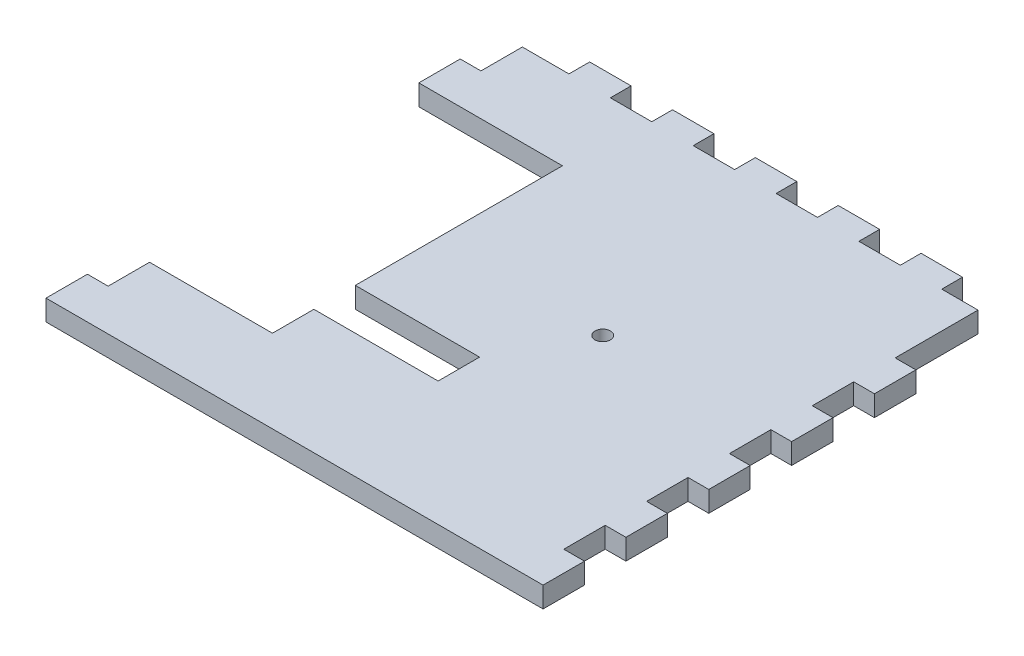
SolidWorks part; units mm, degrees
ref_plane "Front Plane" through (0, 0, 0) normal (0, 0, 1) x (1, 0, 0)
ref_plane "Top Plane" through (0, 0, 0) normal (0, 1, 0) x (1, 0, 0)
ref_plane "Right Plane" through (0, 0, 0) normal (1, 0, 0) x (0, 0, -1)
sketch "Sketch1" plane through (0, 0, 0) normal (0, 1, 0) x (1, 0, 0)
  line L1 (-139.7, -139.7) -> (139.7, -139.7)
  line L2 (-139.7, -139.7) -> (-139.7, 139.7)
  line L3 (-139.7, 139.7) -> (139.7, 139.7)
  line L4 (139.7, -139.7) -> (139.7, 139.7)
  line L5 (-139.7, -139.7) -> (139.7, 139.7) construction
  line L6 (-139.7, 139.7) -> (139.7, -139.7) construction
  point P0 (0, 0)
  dimension "D1" = 279.4
  dimension "D2" = 279.4
extrude "Boss-Extrude1" add sketch "Sketch1" along normal blind 12.7
sketch "Sketch2" plane through (139.7, 0, 0) normal (1, 0, 0) x (0, 0, -1)
  line L0 (-139.7, 12.7) -> (139.7, 12.7) construction
  line L1 (-139.7, 0) -> (-114.3, 0)
  line L2 (-139.7, 0) -> (-139.7, 12.7)
  line L3 (-139.7, 12.7) -> (-114.3, 12.7)
  line L4 (-114.3, 0) -> (-114.3, 12.7)
  dimension "D1" = 25.4
extrude "Boss-Extrude2" add sketch "Sketch2" along normal blind 12.7
pattern_linear "LPattern1" count 5 spacing 50.8 along (0, 0, -1) of "Boss-Extrude2"
mirror "Mirror1" about plane through (0, 0, 0) normal (1, 0, 0) of "LPattern1"
sketch "Sketch3" plane through (0, 0, -139.7) normal (0, 0, -1) x (-1, 0, 0)
  line L0 (-139.7, 12.7) -> (139.7, 12.7) construction
  line L1 (-117.475, 12.7) -> (-92.075, 12.7)
  line L2 (-117.475, 12.7) -> (-117.475, 0)
  line L3 (-117.475, 0) -> (-92.075, 0)
  line L4 (-92.075, 12.7) -> (-92.075, 0)
  line L5 (-139.7, 0) -> (139.7, 0) construction
  line L7 (-152.4, 0) -> (-152.4, 12.7) construction
  dimension "D1" = 34.925
  dimension "D2" = 25.4
extrude "Boss-Extrude3" add sketch "Sketch3" along normal blind 12.7
pattern_linear "LPattern2" count 5 spacing 50.8 along (-1, 0, 0) of "Boss-Extrude3"
sketch "Sketch6" plane through (0, 12.7, 0) normal (0, 1, 0) x (1, 0, 0)
  line L0 (41.275, 139.7) -> (15.875, 139.7) construction
  line L1 (139.7, -12.7) -> (139.7, 12.7) construction
  circle A0 centre (38.1, 11.176) radius 4.7625
  dimension "D1" = 128.524
  dimension "D3" = 9.525
  dimension "D2" = 101.6
extrude "Cut-Extrude1" cut sketch "Sketch6" against normal through all
sketch "Sketch8" plane through (0, 12.7, 0) normal (0, 1, 0) x (1, 0, 0)
  line L1 (-152.4, 88.9) -> (-64.3339, 88.9)
  line L2 (-152.4, 88.9) -> (-152.4, -88.9)
  line L3 (-152.4, -88.9) -> (-64.3339, -88.9)
  line L4 (-64.3339, 88.9) -> (-64.3339, -88.9)
  dimension "D1" = 177.8
extrude "Cut-Extrude3" cut sketch "Sketch8" against normal through all
sketch "Sketch7" plane through (0, 12.7, 0) normal (0, 1, 0) x (1, 0, 0)
  line L2 (-111.125, 139.7) -> (-139.7, 139.7) construction
  line L3 (-139.7, 139.7) -> (-139.7, 88.9) construction
  circle A0 centre (-101.6, 65.278) radius 5.08
  circle A1 centre (-101.6, 27.686) radius 5.08
  dimension "D1" = 10.16
  dimension "D2" = 10.16
  dimension "D3" = 38.1
  dimension "D5" = 37.592
  dimension "D6" = 74.422
sketch "Sketch9" plane through (-139.7, 0, 0) normal (-1, 0, 0) x (0, 0, 1)
  line L0 (153.67, 0) -> (-153.67, 0) construction
  line L1 (-88.9, 12.7) -> (-114.3, 12.7)
  line L2 (-88.9, 12.7) -> (-88.9, 0)
  line L3 (-88.9, 0) -> (-114.3, 0)
  line L4 (-114.3, 12.7) -> (-114.3, 0)
  dimension "D1" = 25.4
extrude "Boss-Extrude4" add sketch "Sketch9" along normal blind 12.7
sketch "Sketch11" plane through (-64.3339, 0, 0) normal (-1, 0, 0) x (0, 0, 1)
  line L6 (88.9, 0) -> (-88.9, 0) construction
  line L7 (63.5, 0) -> (38.1, 0)
  line L8 (63.5, 0) -> (63.5, 12.7)
  line L9 (63.5, 12.7) -> (38.1, 12.7)
  line L10 (38.1, 0) -> (38.1, 12.7)
  line L11 (88.9, 12.7) -> (-88.9, 12.7) construction
  line L12 (88.9, 0) -> (88.9, 12.7) construction
  dimension "D1" = 25.4
  dimension "D2" = 25.4
extrude "Cut-Extrude4" cut sketch "Sketch11" against normal blind 76.2
